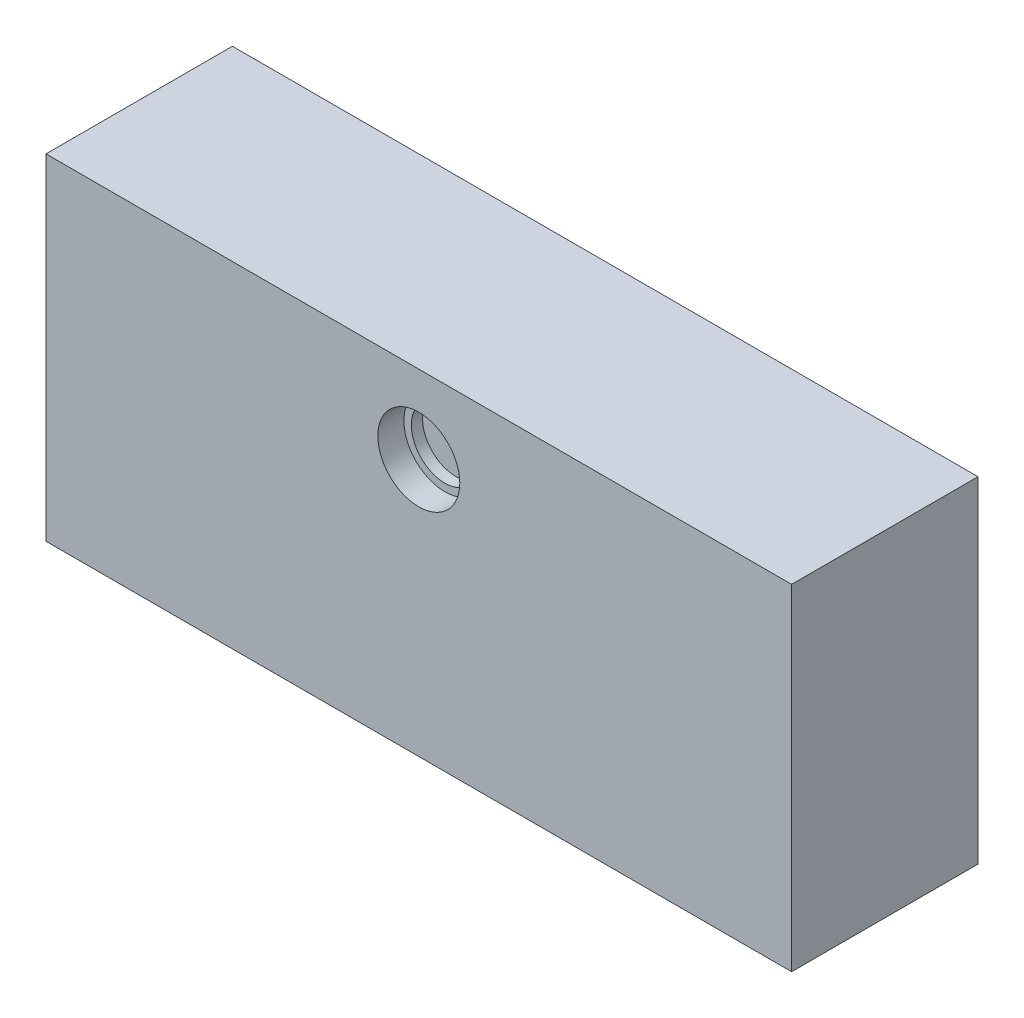
SolidWorks part; units mm, degrees
ref_plane "Front Plane" through (0, 0, 0) normal (0, 0, 1) x (1, 0, 0)
ref_plane "Top Plane" through (0, 0, 0) normal (0, 1, 0) x (1, 0, 0)
ref_plane "Right Plane" through (0, 0, 0) normal (1, 0, 0) x (0, 0, -1)
sketch "Sketch1" plane through (0, 0, 0) normal (0, 0, 1) x (1, 0, 0)
  line L1 (100, -45) -> (-100, -45)
  line L2 (100, -45) -> (100, 45)
  line L3 (100, 45) -> (-100, 45)
  line L4 (-100, -45) -> (-100, 45)
  line L5 (100, -45) -> (-100, 45) construction
  line L6 (100, 45) -> (-100, -45) construction
  point P0 (0, 0)
  dimension "D1" = 200
  dimension "D2" = 90
extrude "Boss-Extrude1" add sketch "Sketch1" along normal mid plane 50
sketch "Sketch2" plane through (0, 0, 25) normal (0, 0, 1) x (1, 0, 0)
  line L0 (100, 45) -> (-100, 45) construction
  circle A0 centre (0, 24) radius 11
  circle A1 centre (0, 24) radius 9
  dimension "D1" = 21
  dimension "D2" = 22
  dimension "D3" = 18
extrude "Cut-Extrude1" cut sketch "Sketch2" against normal blind 10 contours A1
extrude "Cut-Extrude2" cut sketch "Sketch2<4>" against normal blind 7
sketch "Sketch2<4>" plane through (0, 0, 25) normal (0, 0, 1) x (1, 0, 0) same geometry as "Sketch2"
sketch "Sketch3" plane through (0, -45, 0) normal (0, -1, 0) x (1, 0, 0)
  line L0 (-100, 25) -> (-100, -25) construction
  line L1 (100, 25) -> (100, -25) construction
  circle A0 centre (-50, 0) radius 5
  circle A1 centre (50, 0) radius 5
  dimension "D1" = 10
  dimension "D3" = 10
  dimension "D2" = 50
  dimension "D4" = 50
extrude "Cut-Extrude3" cut sketch "Sketch3" against normal blind 15
sketch "Sketch4" plane through (0, 0, -25) normal (0, 0, -1) x (-1, 0, 0)
  line L0 (100, -45) -> (-100, -45) construction
  line L1 (-100, -45) -> (-100, 45) construction
  line L2 (100, 45) -> (100, -45) construction
  circle A0 centre (-50, -5) radius 5
  circle A1 centre (50, -5) radius 5
  dimension "D1" = 40
  dimension "D2" = 50
  dimension "D3" = 40
  dimension "D4" = 10
  dimension "D5" = 50
  dimension "D6" = 10
extrude "Cut-Extrude4" cut sketch "Sketch4" against normal blind 15
